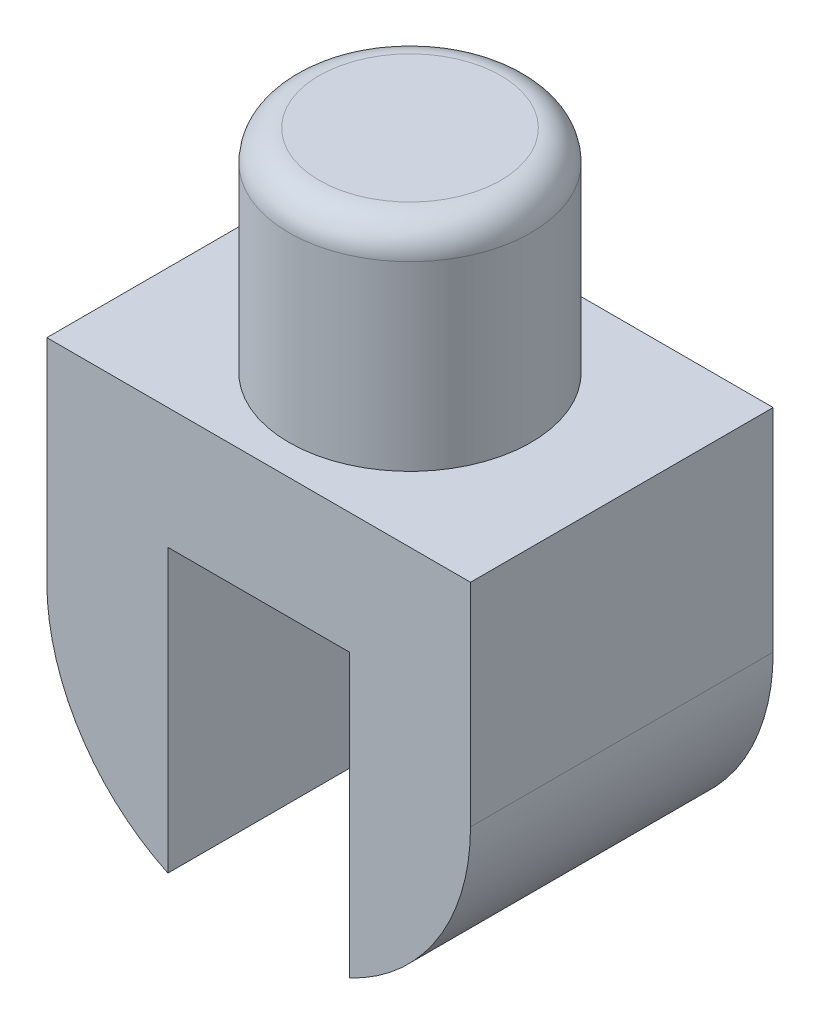
SolidWorks part; units mm, degrees
material "ABS"
ref_plane "Front" through (0, 0, 0) normal (0, 0, 1) x (1, 0, 0)
ref_plane "Top" through (0, 0, 0) normal (0, 1, 0) x (1, 0, 0)
ref_plane "Right" through (0, 0, 0) normal (1, 0, 0) x (0, 0, -1)
sketch "Sketch1" plane through (0, 0, 0) normal (0, 0, 1) x (1, 0, 0)
  line L0 (-3.5, 0) -> (3.5, 0) construction
  line L2 (-3.5, 0) -> (-3.5, 3.5)
  line L3 (-3.5, 3.5) -> (3.5, 3.5)
  line L4 (3.5, 0) -> (3.5, 3.5)
  arc A0 (-3.5, 0) -> (3.5, 0) centre (0, 0) ccw
  dimension "D1" = 7
  dimension "D2" = 3.5
sketch "Sketch2" plane through (0, 0, 0) normal (0, 1, 0) x (1, 0, 0)
  line L1 (1.5, 3) -> (-1.5, 3)
  line L2 (1.5, 3) -> (1.5, -3)
  line L3 (1.5, -3) -> (-1.5, -3)
  line L4 (-1.5, 3) -> (-1.5, -3)
  line L5 (1.5, 3) -> (-1.5, -3) construction
  line L6 (1.5, -3) -> (-1.5, 3) construction
  point P0 (0, 0)
  dimension "D1" = 6
  dimension "D2" = 3
sketch "Sketch3" plane through (0, 0, 0) normal (0, 1, 0) x (1, 0, 0)
  circle A0 centre (0, 0) radius 2
  dimension "D1" = 4
sketch "Sketch4" plane through (0, 0, 0) normal (0, 0, 1) x (1, 0, 0)
  circle A0 centre (0, 0) radius 2
  dimension "D1" = 4
extrude "Hand" add sketch "Sketch1" along normal blind 2.5 and the other way blind 2.5
extrude "Wrist" add sketch "Sketch3" along normal blind 7
extrude "Hand hole" [suppressed] cut sketch "Sketch4" against normal through all and the other way through all contours A0
extrude "Finger gap" cut sketch "Sketch2" against normal through all and the other way blind 1.5
fillet "Smoothing edges" [suppressed] radius 0.1
fillet "Easy insert" radius 0.5 1 edges at (0, 7, 2)
scale "Scale1" scale about centroid uniform scaling yes scale factor 2
